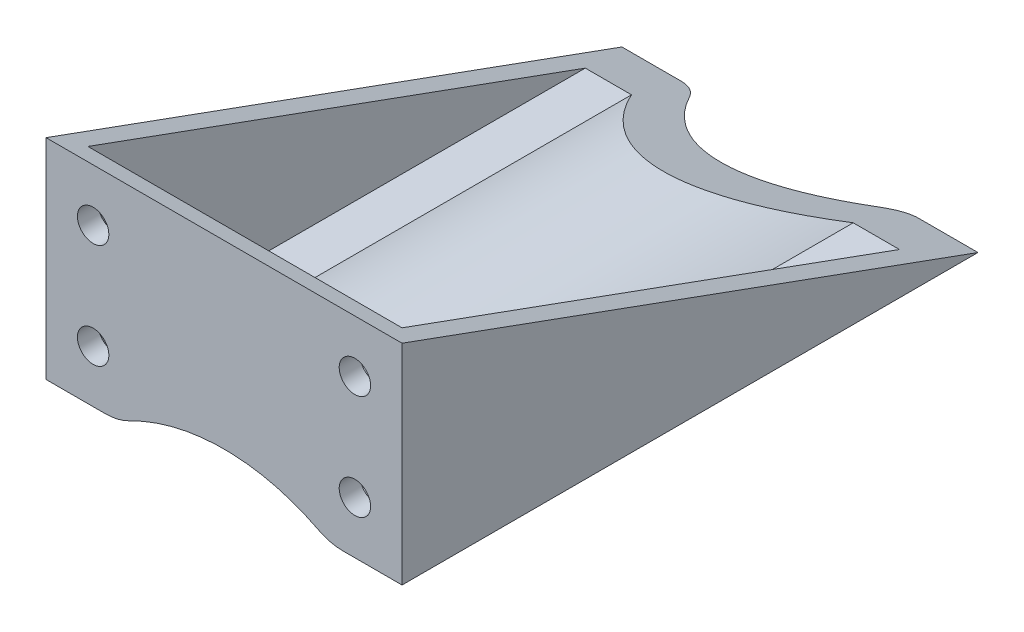
SolidWorks part; units mm, degrees
ref_plane "Alzado" through (0, 0, 0) normal (0, 0, 1) x (1, 0, 0)
ref_plane "Planta" through (0, 0, 0) normal (0, 1, 0) x (1, 0, 0)
ref_plane "Vista lateral" through (0, 0, 0) normal (1, 0, 0) x (0, 0, -1)
sketch "Croquis4" plane through (0, 0, 0) normal (1, 0, 0) x (0, 0, -1)
  line L0 (0, 0) -> (55, 0)
  line L1 (55, 0) -> (0, 20)
  line L2 (0, 20) -> (0, 0)
  dimension "D1" = 20
  dimension "D2" = 55
extrude "Saliente-Extruir3" add sketch "Croquis4" along normal blind 34
sketch "Croquis5" plane through (0, 0, 0) normal (0, 0, 1) x (1, 0, 0)
  line L0 (0, 0) -> (34, 20) construction
  line L2 (29.5, 5) -> (4.5, 5)
  line L3 (29.5, 5) -> (29.5, 15)
  line L4 (29.5, 15) -> (4.5, 15)
  line L5 (4.5, 5) -> (4.5, 15)
  line L6 (29.5, 5) -> (4.5, 15) construction
  line L7 (29.5, 15) -> (4.5, 5) construction
  circle A0 centre (4.5, 15) radius 1.5
  circle A1 centre (29.5, 15) radius 1.5
  circle A2 centre (29.5, 5) radius 1.5
  circle A3 centre (4.5, 5) radius 1.5
  point P4 (17, 10)
  dimension "D3" = 2
  dimension "D1" = 25
  dimension "D2" = 10
  dimension "D4" = 2
sketch "Croquis6" plane through (0, 0, 0) normal (0, 0, 1) x (1, 0, 0)
  line L0 (17, 0) -> (17, -17) construction
  line L1 (34, 0) -> (0, 0) construction
  circle A0 centre (17, -17) radius 19.75
  dimension "D1" = 39.5
  dimension "D2" = 17
extrude "Cortar-Extruir2" cut sketch "Croquis6" against normal through all
shell "Vaciado3" thickness 2 removed face at (17, 7.125, -35.4062)
extrude "Cortar-Extruir3" cut sketch "Croquis5" against normal blind 10 contours A0 | A1 | A2 | A3
fillet "Redondeo1" radius 5 2 edges at (6.947, 0, -27.5) (27.053, 0, -27.5)
